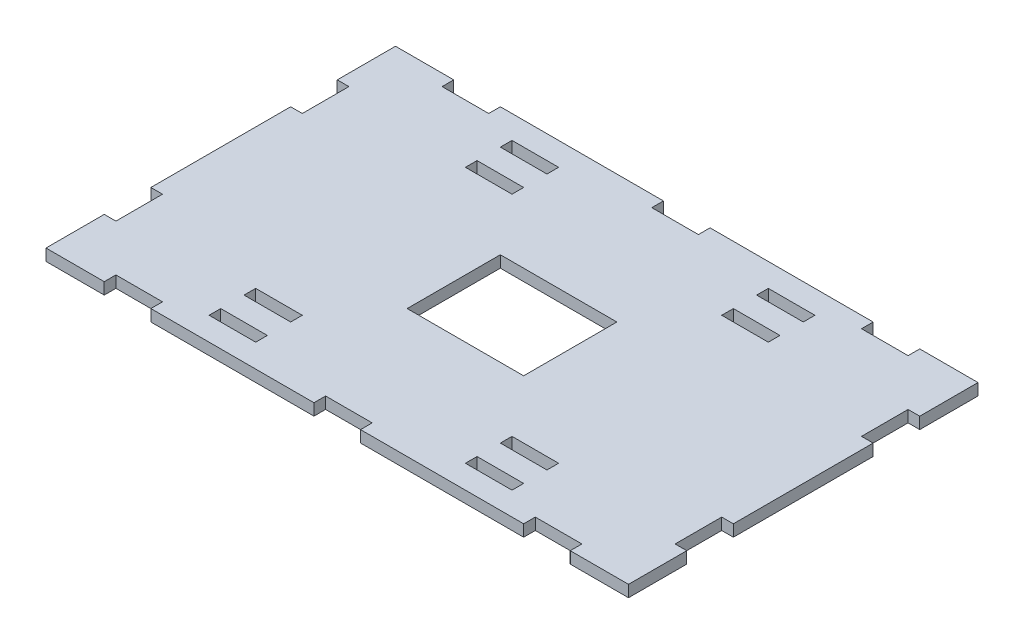
SolidWorks part; units mm, degrees
material "Very Low Density PE (SS)"
ref_plane "Front Plane" through (0, 0, 0) normal (0, 0, 1) x (1, 0, 0)
ref_plane "Top Plane" through (0, 0, 0) normal (0, 1, 0) x (1, 0, 0)
ref_plane "Right Plane" through (0, 0, 0) normal (1, 0, 0) x (0, 0, -1)
sketch "Sketch1" plane through (0, 0, 0) normal (0, 1, 0) x (1, 0, 0)
  line L0 (-125, 0) -> (125, 0) construction
  line L1 (-125, 75) -> (-100, 75)
  line L2 (-125, 75) -> (-125, 50)
  line L3 (-125, -75) -> (-100, -75)
  line L4 (125, 75) -> (125, 50)
  line L5 (0, 75) -> (0, -75) construction
  line L6 (-125, -55) -> (125, -55) construction
  line L11 (-65, -45) -> (-45, -45)
  line L12 (-65, -60) -> (-45, -60)
  line L25 (-65, -60) -> (-65, -65)
  line L26 (-25, 20) -> (25, 20)
  line L27 (-25, 20) -> (-25, -20)
  line L28 (-25, -20) -> (25, -20)
  line L29 (25, 20) -> (25, -20)
  line L30 (-25, 20) -> (25, -20) construction
  line L31 (-25, -20) -> (25, 20) construction
  line L32 (-65, -65) -> (-45, -65)
  line L33 (-45, -60) -> (-45, -65)
  line L34 (-45, -50) -> (-45, -45)
  line L35 (-65, -50) -> (-45, -50)
  line L36 (-65, -50) -> (-65, -45)
  line L37 (65, -65) -> (45, -65)
  line L38 (45, -60) -> (45, -65)
  line L39 (65, -60) -> (45, -60)
  line L40 (65, -60) -> (65, -65)
  line L41 (65, -50) -> (65, -45)
  line L42 (65, -50) -> (45, -50)
  line L43 (45, -50) -> (45, -45)
  line L44 (65, -45) -> (45, -45)
  line L45 (65, 50) -> (45, 50)
  line L46 (45, 50) -> (45, 45)
  line L47 (65, 45) -> (45, 45)
  line L48 (65, 50) -> (65, 45)
  line L49 (65, 60) -> (65, 65)
  line L50 (65, 60) -> (45, 60)
  line L51 (45, 60) -> (45, 65)
  line L52 (65, 65) -> (45, 65)
  line L53 (-65, 65) -> (-45, 65)
  line L54 (-45, 60) -> (-45, 65)
  line L55 (-65, 60) -> (-45, 60)
  line L56 (-65, 60) -> (-65, 65)
  line L57 (-65, 50) -> (-65, 45)
  line L58 (-65, 50) -> (-45, 50)
  line L59 (-45, 50) -> (-45, 45)
  line L60 (-65, 45) -> (-45, 45)
  line L61 (100, -70) -> (80, -70)
  line L63 (-100, -75) -> (-100, -70)
  line L64 (-100, -70) -> (-80, -70)
  line L65 (-80, -75) -> (-80, -70)
  line L66 (80, -75) -> (80, -70)
  line L68 (100, -75) -> (100, -70)
  line L69 (10, -75) -> (80, -75)
  line L70 (-10, -70) -> (10, -70)
  line L71 (-10, -70) -> (-10, -75)
  line L73 (10, -70) -> (10, -75)
  line L74 (-10, -70) -> (10, -75) construction
  line L75 (-10, -75) -> (10, -70) construction
  line L76 (-80, -75) -> (-10, -75)
  line L77 (100, -75) -> (125, -75)
  line L78 (100, 75) -> (100, 70)
  line L79 (80, 75) -> (80, 70)
  line L80 (100, 70) -> (80, 70)
  line L81 (10, 70) -> (10, 75)
  line L82 (-10, 70) -> (10, 70)
  line L83 (-10, 70) -> (-10, 75)
  line L84 (-80, 75) -> (-80, 70)
  line L85 (-100, 70) -> (-80, 70)
  line L86 (-100, 75) -> (-100, 70)
  line L87 (-10, 75) -> (0, 75) construction
  line L88 (10, 75) -> (80, 75)
  line L89 (0, 75) -> (10, 75) construction
  line L90 (-100, 75) -> (-80, 75) construction
  line L91 (-80, 75) -> (-10, 75)
  line L92 (80, 75) -> (100, 75) construction
  line L93 (100, 75) -> (125, 75)
  line L94 (125, -30) -> (120, -30)
  line L95 (125, 50) -> (120, 50)
  line L96 (125, 50) -> (125, 30) construction
  line L97 (125, 30) -> (120, 30)
  line L98 (120, 50) -> (120, 30)
  line L99 (120, -50) -> (120, -30)
  line L100 (125, -50) -> (120, -50)
  line L101 (125, -50) -> (125, -30) construction
  line L102 (125, 50) -> (125, 30) construction
  line L103 (125, 30) -> (125, -30)
  line L104 (125, -30) -> (125, -50) construction
  line L105 (125, -50) -> (125, -75)
  line L106 (-125, -30) -> (-120, -30)
  line L107 (-120, -50) -> (-120, -30)
  line L108 (-125, -50) -> (-120, -50)
  line L109 (-125, 30) -> (-120, 30)
  line L110 (-125, 50) -> (-120, 50)
  line L111 (-120, 50) -> (-120, 30)
  line L112 (-125, 50) -> (-125, 30) construction
  line L113 (-125, 30) -> (-125, -30)
  line L114 (-125, -30) -> (-125, -50) construction
  line L115 (-125, -50) -> (-125, -75)
  point P0 (0, 0)
  point P29 (0, 0)
  point P57 (0, -72.5)
  dimension "D2" = 150
  dimension "D3" = 5
  dimension "D4" = 20
  dimension "D5" = 25
  dimension "D6" = 20
  dimension "D7" = 40
  dimension "D8" = 50
  dimension "D9" = 5
  dimension "D10" = 45
  dimension "D11" = 20
  dimension "D12" = 5
  dimension "D13" = 20
  dimension "D15" = 25
  dimension "D16" = 20
  dimension "D17" = 5
  dimension "D18" = 250
extrude "Boss-Extrude1" add sketch "Sketch1" along normal blind 5
